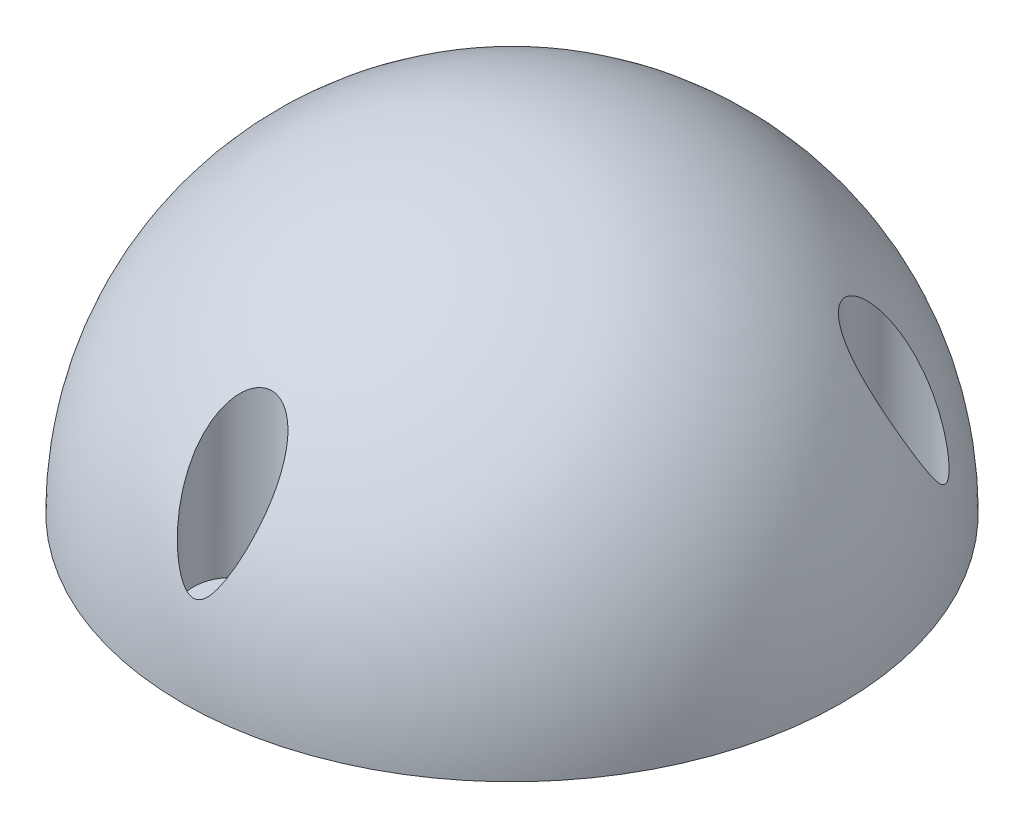
SolidWorks part; units mm, degrees
material "ABS"
ref_plane "정면" through (0, 0, 0) normal (0, 0, 1) x (1, 0, 0)
ref_plane "윗면" through (0, 0, 0) normal (0, 1, 0) x (1, 0, 0)
ref_plane "우측면" through (0, 0, 0) normal (1, 0, 0) x (0, 0, -1)
sketch "스케치1" plane through (0, 0, 0) normal (0, 0, 1) x (1, 0, 0)
  line L0 (-29.5, 0) -> (29.5, 0)
  line L1 (0, 0) -> (0, 39.3704) construction
  arc A0 (29.5, 0) -> (-29.5, 0) centre (0, 0) ccw
  point P6 (0, 0)
  dimension "D1" = 59
revolve "회전1" add sketch "스케치1" angle 360 about L1 region at (-12.5202, 12.5202, 0)
sketch "스케치2" plane through (0, 0, 0) normal (0, -1, 0) x (1, 0, 0)
  circle A0 centre (0, 0) radius 25
  circle A1 centre (0, 25) radius 3.5
  circle A2 centre (0, 25) radius 2
  circle A3 centre (21.6506, -12.5) radius 2
  circle A4 centre (21.6506, -12.5) radius 3.5
  circle A5 centre (-21.6506, -12.5) radius 2
  circle A6 centre (-21.6506, -12.5) radius 3.5
  point P3 (0, 25)
  point P16 (0, 0)
  dimension "D1" = 50
  dimension "D2" = 7
  dimension "D3" = 4
  dimension "D4" = 3
extrude "컷-돌출6" cut sketch "스케치2" against normal blind 40 from offset 5 contours A1 | A6 | A4 offset against normal yes
extrude "컷-돌출7" cut sketch "스케치2<9>" against normal blind 40 contours A5 | A3 | A2
sketch "스케치2<9>" plane through (0, 0, 0) normal (0, -1, 0) x (1, 0, 0) same geometry as "스케치2"
